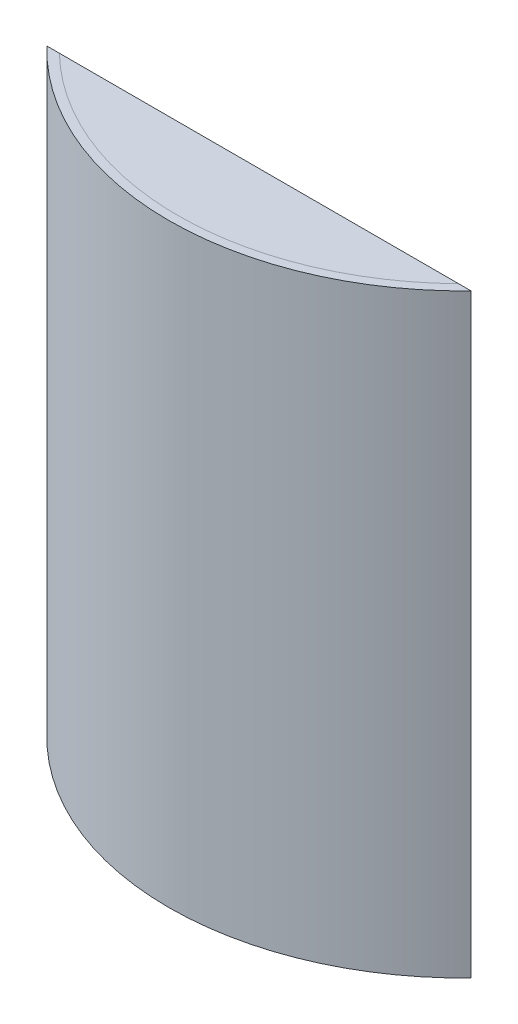
SolidWorks part; units mm, degrees
ref_plane "Front Plane" through (0, 0, 0) normal (0, 0, 1) x (1, 0, 0)
ref_plane "Top Plane" through (0, 0, 0) normal (0, 1, 0) x (1, 0, 0)
ref_plane "Right Plane" through (0, 0, 0) normal (1, 0, 0) x (0, 0, -1)
sketch "Sketch1" plane through (0, 0, 0) normal (0, 1, 0) x (1, 0, 0)
  line L0 (0, -23.4644) -> (0, -66.5001) construction
  line L1 (-72, -69.3974) -> (72, -69.3974)
  line L2 (-64.5571, -72.3974) -> (64.5571, -72.3974)
  arc A0 (-72, -69.3974) -> (72, -69.3974) centre (0, 0) ccw
  arc A1 (-64.5571, -72.3974) -> (64.5571, -72.3974) centre (0, 0) ccw
  arc A2 (64.5571, -72.3974) -> (67.7717, -69.3974) centre (0, 0) ccw
  arc A3 (-67.7717, -69.3974) -> (-64.5571, -72.3974) centre (0, 0) ccw
  arc A5 (-64.5571, -72.3974) -> (64.5571, -72.3974) centre (0, 0) ccw construction
  point P9 (0, -69.3974)
  dimension "D1" = 200
  dimension "D2" = 72
  dimension "D3" = 3
extrude "Boss-Extrude3" add sketch "Sketch1" along normal blind 202 contours A3 L1 A0 A2 A1 region at (-69.8858, 0, 70.8696)
extrude "Boss-Extrude4" add sketch "Sketch1<6>" along normal blind 2 contours L1 A0
sketch "Sketch1<6>" plane through (0, 0, 0) normal (0, 1, 0) x (1, 0, 0) same geometry as "Sketch1"
sketch "Sketch7" plane through (0, 202, 0) normal (0, 1, 0) x (1, 0, 0)
  line L0 (67.7717, -69.3974) -> (-67.7717, -69.3974)
  arc M1 (67.7717, -69.3974) -> (-67.7717, -69.3974) centre (0, 0) cw
extrude "Boss-Extrude5" add sketch "Sketch7" against normal blind 2 separate body contours L0 M1 region at (0, 202, 80.5852)
